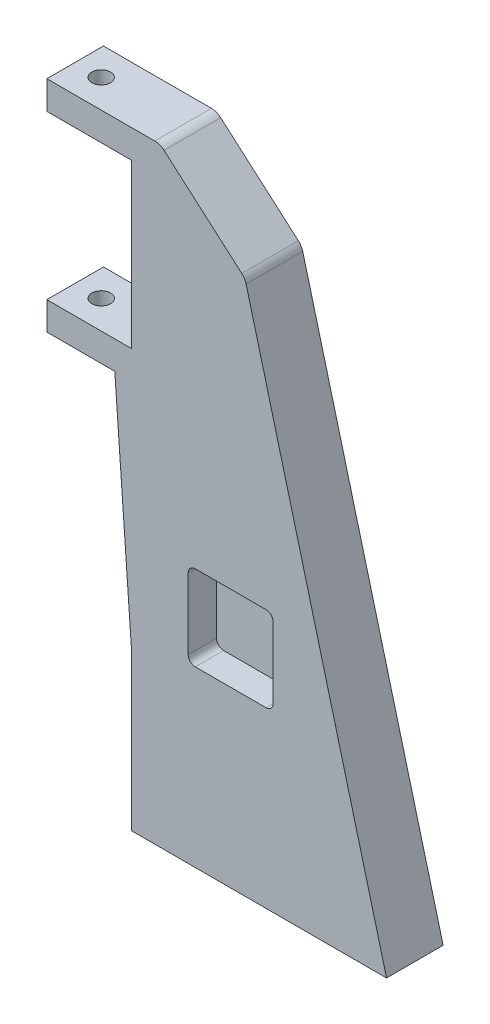
SolidWorks part; units mm, degrees
ref_plane "Front Plane" through (0, 0, 0) normal (0, 0, 1) x (1, 0, 0)
ref_plane "Top Plane" through (0, 0, 0) normal (0, 1, 0) x (1, 0, 0)
ref_plane "Right Plane" through (0, 0, 0) normal (1, 0, 0) x (0, 0, -1)
sketch "Sketch1" plane through (0, 0, 0) normal (0, 0, 1) x (1, 0, 0)
  line L0 (0, 0) -> (0, 12.7)
  line L1 (0, 12.7) -> (50.8, 12.7)
  line L2 (50.8, 12.7) -> (88.9, -20.5102)
  line L3 (0, 0) -> (38.0187, 0)
  line L4 (38.0187, 0) -> (38.0187, -73.1523)
  line L5 (38.0187, -73.1523) -> (0, -73.1523)
  line L6 (0, -73.1523) -> (0, -85.7639)
  line L7 (0, -85.7639) -> (30.48, -85.7639)
  line L10 (38.0187, -260.5159) -> (152.4, -260.5159)
  line L11 (152.4, -260.5159) -> (88.9, -20.5102)
  line L15 (30.48, -85.7639) -> (38.0187, -190.6965)
  line L16 (38.0187, -190.6965) -> (38.0187, -260.5159)
  dimension "D1" = 50.8
  dimension "D2" = 12.7
  dimension "D3" = 38.0187
  dimension "D4" = 73.1523
  dimension "D5" = 152.4
  dimension "D6" = 38.1
  dimension "D7" = 30.48
  dimension "D9" = 12.6117
  dimension "D10" = 174.752
extrude "Boss-Extrude1" add sketch "Sketch1" along normal blind 25.4
sketch "Sketch2" plane through (0, 0, 25.4) normal (0, 0, 1) x (1, 0, 0)
  line L0 (0, -85.7639) -> (30.48, -85.7639) construction
  line L1 (101.5187, -182.5379) -> (63.4187, -182.5379)
  line L2 (101.5187, -182.5379) -> (101.5187, -144.4379)
  line L3 (101.5187, -144.4379) -> (63.4187, -144.4379)
  line L4 (63.4187, -182.5379) -> (63.4187, -144.4379)
  line L5 (38.0187, -190.6965) -> (38.0187, -260.5159) construction
  dimension "D1" = 38.1
  dimension "D2" = 38.1
  dimension "D3" = 58.674
  dimension "D4" = 25.4
extrude "Cut-Extrude1" cut sketch "Sketch2" against normal offset from surface (12.7 mm away) 12.7 up to face at (39.5546, -85.3892, 0)
sketch "Sketch6" plane through (0, 12.7, 0) normal (0, 1, 0) x (1, 0, 0)
  line L0 (0, -25.4) -> (0, 0) construction
  line L1 (50.8, -25.4) -> (0, -25.4) construction
  circle A0 centre (11.684, -12.7) radius 4.191
  dimension "D3" = 8.382
  dimension "D1" = 11.684
  dimension "D2" = 12.7
extrude "Cut-Extrude2" cut sketch "Sketch6" against normal through all
sketch "Sketch7" plane through (0, -260.5159, 0) normal (0, -1, 0) x (-1, 0, 0)
  line L0 (-152.4, -25.4) -> (-152.4, 0) construction
  line L1 (-38.0187, -25.4) -> (-152.4, -25.4) construction
  circle A0 centre (-139.7, -12.7) radius 4.191
  circle A1 centre (-63.5, -12.7) radius 4.191
  dimension "D3" = 8.382
  dimension "D4" = 8.382
  dimension "D1" = 12.7
  dimension "D2" = 12.7
  dimension "D5" = 12.7
  dimension "D6" = 76.2
extrude "Cut-Extrude3" cut sketch "Sketch7" against normal blind 25.4
fillet "Fillet1" radius 6.35 3 edges at (38.0187, -190.6965, 12.7) (88.9, -20.5102, 12.7) (50.8, 12.7, 12.7)
fillet "Fillet2" radius 3.175 4 edges at (101.5187, -144.4379, 19.05) (63.4187, -144.4379, 19.05) (63.4187, -182.5379, 19.05) (101.5187, -182.5379, 19.05)
